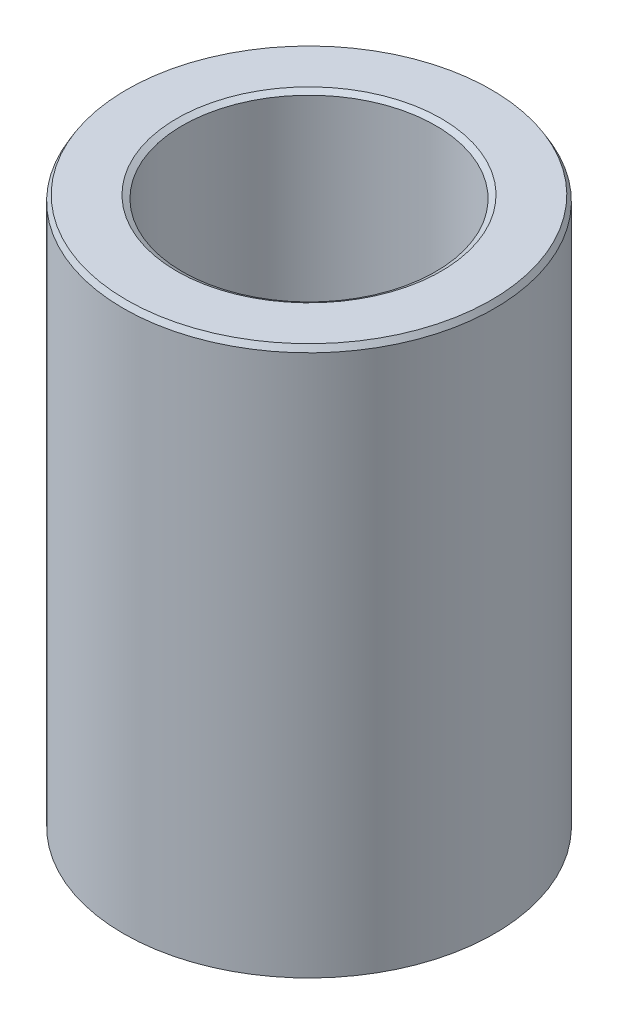
SolidWorks part; units mm, degrees
ref_plane "Front Plane" through (0, 0, 0) normal (0, 0, 1) x (1, 0, 0)
ref_plane "Top Plane" through (0, 0, 0) normal (0, 1, 0) x (1, 0, 0)
ref_plane "Right Plane" through (0, 0, 0) normal (1, 0, 0) x (0, 0, -1)
sketch "Sketch1" plane through (0, 0, 0) normal (0, 1, 0) x (1, 0, 0)
  circle A0 centre (0, 0) radius 52.5
  dimension "SLEEVE_OD" = 105
extrude "Boss-Extrude1" add sketch "Sketch1" along normal blind 155.7006
sketch "Sketch2" plane through (0, 0, 0) normal (0, 1, 0) x (1, 0, 0)
  circle A0 centre (0, 0) radius 35.831
  dimension "BORE_D" = 71.6619
extrude "Cut-Extrude1" cut sketch "Sketch2" along normal through all
chamfer "Chamfer1" distance 1.5934 angle 30 4 edges at (0, 155.7006, 35.831) (0, 0, 35.831) (0, 0, 52.5) (0, 155.7006, 52.5) first distance on face at (0, 155.7006, 35.831) first distance on face at (0, 0, 35.831) first distance on face at (0, 155.7006, 52.5)
